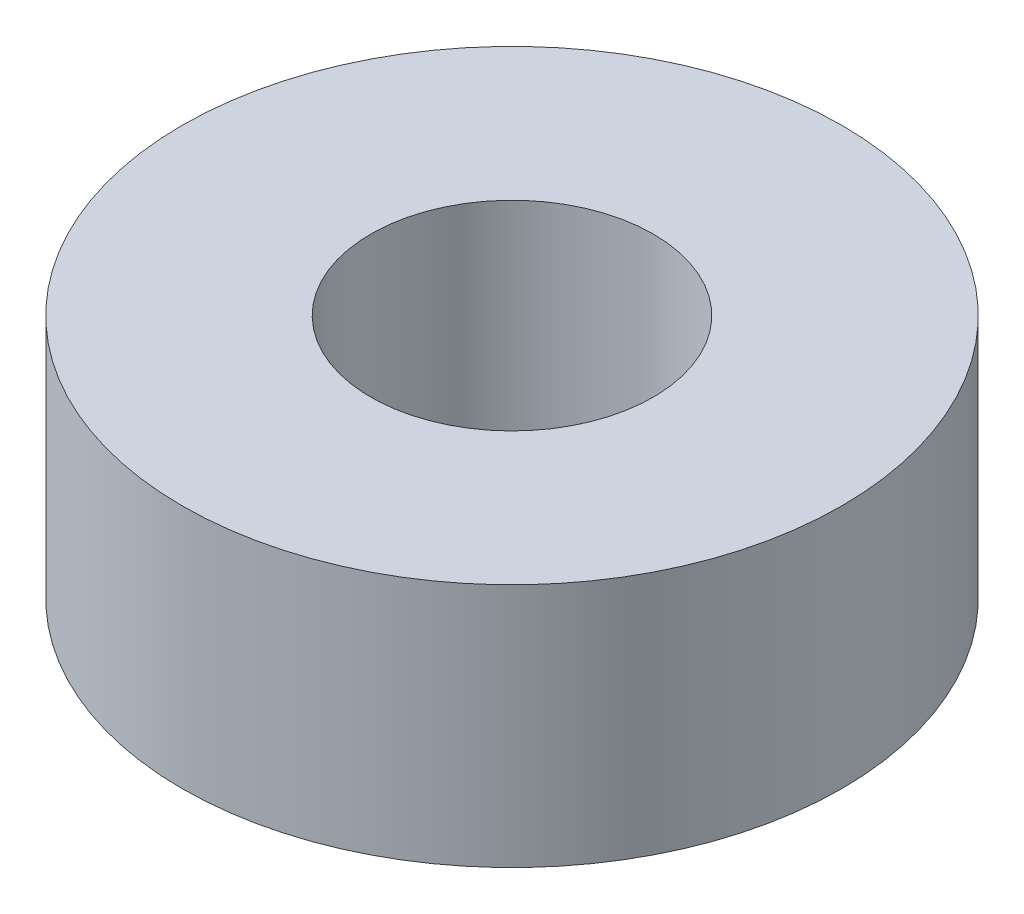
SolidWorks part; units mm, degrees
ref_plane "Front Plane" through (0, 0, 0) normal (0, 0, 1) x (1, 0, 0)
ref_plane "Top Plane" through (0, 0, 0) normal (0, 1, 0) x (1, 0, 0)
ref_plane "Right Plane" through (0, 0, 0) normal (1, 0, 0) x (0, 0, -1)
sketch "Sketch1" plane through (0, 0, 0) normal (0, 1, 0) x (1, 0, 0)
  circle A0 centre (0, 0) radius 17.5
  dimension "FLANGE_OD" = 35
extrude "Boss-Extrude1" add sketch "Sketch1" along normal blind 13
sketch "Sketch2" plane through (0, 0, 0) normal (0, 1, 0) x (1, 0, 0)
  circle A0 centre (0, 0) radius 7.5
  dimension "BORE_D" = 15
extrude "Cut-Extrude1" cut sketch "Sketch2" along normal through all
sketch "Sketch3" plane through (0, 13, 0) normal (0, 1, 0) x (1, 0, 0)
  circle A0 centre (0, 0) radius 5.614 construction
  circle A1 centre (-5.614, 0) radius 1.6823
  dimension "BOLT_D" = 3.3647
  dimension "BOLT_PCD" = 11.2281
extrude "Cut-Extrude2" cut sketch "Sketch3" against normal blind 8.5087 rebuild error yes
pattern_circular "CirPattern1" count 6 over 360 rebuild error yes
